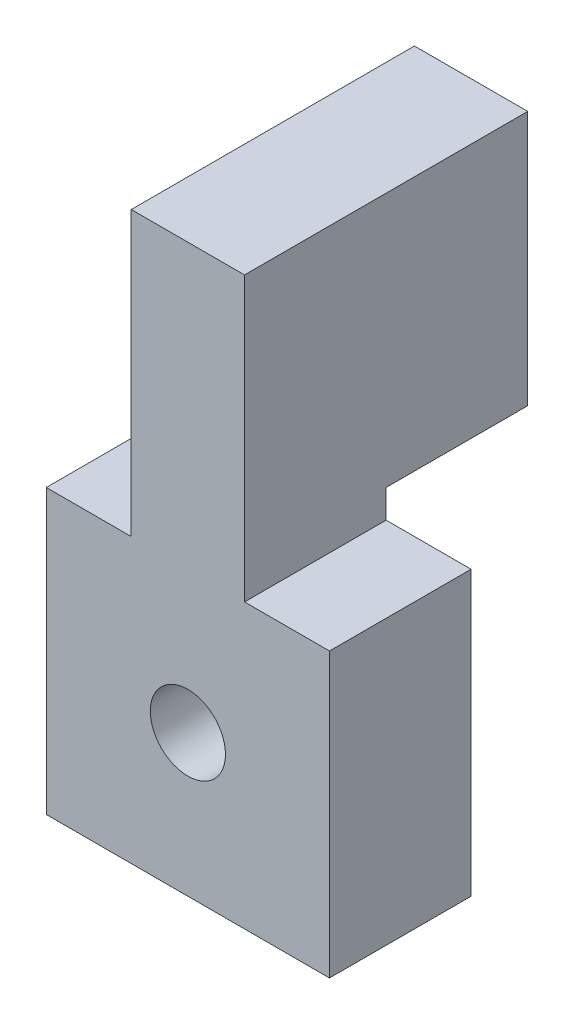
SolidWorks part; units mm, degrees
ref_plane "Front Plane" through (0, 0, 0) normal (0, 0, 1) x (1, 0, 0)
ref_plane "Top Plane" through (0, 0, 0) normal (0, 1, 0) x (1, 0, 0)
ref_plane "Right Plane" through (0, 0, 0) normal (1, 0, 0) x (0, 0, -1)
sketch "Sketch1" plane through (0, 0, 0) normal (0, 0, 1) x (1, 0, 0)
  line L1 (-10, 10) -> (10, 10)
  line L2 (-10, 10) -> (-10, -10)
  line L3 (-10, -10) -> (10, -10)
  line L4 (10, 10) -> (10, -10)
  line L5 (-10, 10) -> (10, -10) construction
  line L6 (-10, -10) -> (10, 10) construction
  line L7 (-4, 30) -> (4, 30)
  line L8 (-4, 30) -> (-4, 10)
  line L9 (-4, 10) -> (4, 10)
  line L10 (4, 30) -> (4, 10)
  line L11 (-4, 30) -> (4, 10) construction
  line L12 (-4, 10) -> (4, 30) construction
  point P0 (0, 0)
  point P6 (0, 20)
  dimension "D1" = 20
  dimension "D2" = 20
  dimension "D3" = 8
  dimension "D4" = 20
extrude "Boss-Extrude1" add sketch "Sketch1" along normal blind 10 contours L4 L1 L2 L3 | L10 L7 L8 L1 region at (0, 0, 0) region at (0, 20, 0)
hole_wizard "#4 (0.209) Diameter Hole1" positions "Sketch2" profile "Sketch3" hole size "#4" standard "ANSI Inch" end condition through all
sketch "Sketch2" plane through (0, 0, 10) normal (0, 0, 1) x (1, 0, 0)
  point P0 (0, 0)
sketch "Sketch3" plane through (0, 0, 10) normal (1, 0, 0) x (0, -1, 0)
  line L0 (0, 0) -> (0, 10)
  line L1 (0, 10) -> (2.6543, 10)
  line L2 (2.6543, 10) -> (2.6543, 0)
  line L5 (2.6543, 0) -> (0, 0)
  line L11 (0, -6.35) -> (0, 107.95) construction
  dimension "Thru Hole Dia." = 5.3086
  dimension "Thru Hole Depth" = 10
extrude "Boss-Extrude2" add sketch "Sketch1<3>" against normal blind 10 contours L10 L7 L8 L1 region at (0, 20, 0)
sketch "Sketch1<3>" plane through (0, 0, 0) normal (0, 0, 1) x (1, 0, 0) same geometry as "Sketch1"
sketch "Sketch4" plane through (0, 0, -10) normal (0, 0, -1) x (-1, 0, 0)
  line L0 (4, 30) -> (4, 10) construction
  line L1 (-4, 10) -> (4, 10)
  line L2 (-4, 10) -> (-4, 12)
  line L3 (-4, 12) -> (4, 12)
  line L4 (4, 10) -> (4, 12)
  dimension "D1" = 2
extrude "Cut-Extrude1" cut sketch "Sketch4" against normal up to surface (10 mm away) up to face at (2.6543, 0, 0)
